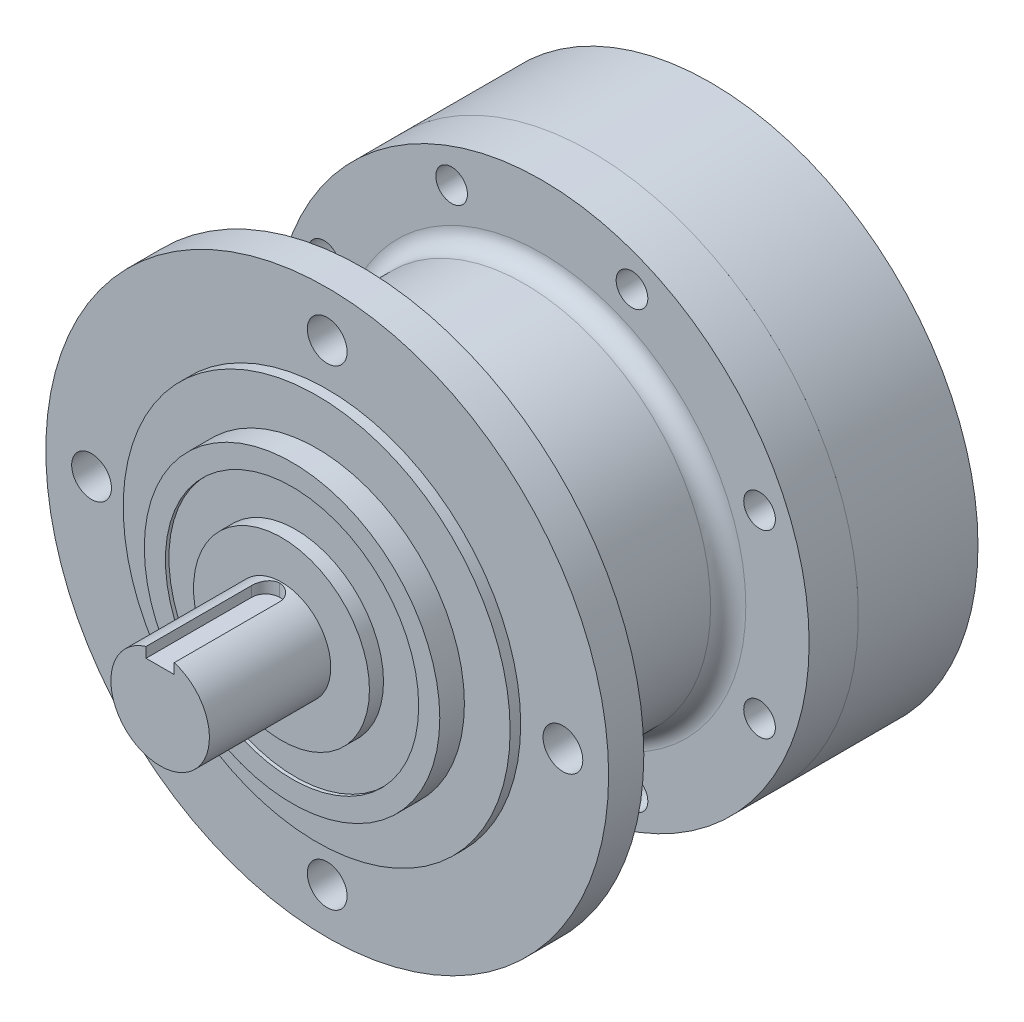
SolidWorks part; units mm, degrees
ref_plane "前视基准面" through (0, 0, 0) normal (0, 0, 1) x (1, 0, 0)
ref_plane "上视基准面" through (0, 0, 0) normal (0, 1, 0) x (1, 0, 0)
ref_plane "右视基准面" through (0, 0, 0) normal (1, 0, 0) x (0, 0, -1)
sketch "草图1" plane through (0, 0, 0) normal (0, 0, 1) x (1, 0, 0)
  circle A0 centre (0, 0) radius 76
  dimension "D1" = 152
extrude "拉伸1" add sketch "草图1" along normal blind 48
sketch "草图2" plane through (0, 0, 48) normal (0, 0, 1) x (1, 0, 0)
  circle A0 centre (0, 0) radius 53
extrude "拉伸2" add sketch "草图2" along normal blind 51
sketch "草图3" plane through (0, 0, 99) normal (0, 0, 1) x (1, 0, 0)
  circle A0 centre (0, 0) radius 80
extrude "拉伸3" add sketch "草图3" along normal blind 10
fillet "圆角1" radius 5 2 edges at (53, 0, 48) (53, 0, 99)
sketch "草图4" plane through (0, 0, 109) normal (0, 0, 1) x (1, 0, 0)
  circle A0 centre (0, 0) radius 55
extrude "拉伸4" add sketch "草图4" along normal blind 3
sketch "草图5" plane through (0, 0, 112) normal (0, 0, 1) x (1, 0, 0)
  circle A0 centre (0, 0) radius 42
extrude "拉伸5" add sketch "草图5" along normal blind 7
sketch "草图6" plane through (0, 0, 119) normal (0, 0, 1) x (1, 0, 0)
  circle A0 centre (0, 0) radius 25
extrude "拉伸6" add sketch "草图6" along normal blind 3
sketch "草图7" plane through (0, 0, 119) normal (0, 0, 1) x (1, 0, 0)
  circle A0 centre (0, 0) radius 36
  circle A1 centre (0, 0) radius 25
extrude "切除-拉伸1" cut sketch "草图7" against normal blind 1
sketch "草图8" plane through (0, 0, 122) normal (0, 0, 1) x (1, 0, 0)
  circle A0 centre (0, 0) radius 14
extrude "拉伸7" add sketch "草图8" along normal blind 34.5
sketch "草图9" plane through (0, 0, 156.5) normal (0, 0, 1) x (1, 0, 0)
  line L1 (-4, 14) -> (-4, 10.5)
  line L2 (4, 14) -> (4, 10.5)
  line L3 (-4, 14) -> (4, 14)
  line L9 (-4, 10.5) -> (4, 10.5)
extrude "切除-拉伸3" cut sketch "草图9" against normal blind 34
fillet "圆角2" radius 4 2 edges at (-4, 11.9582, 122.5) (4, 11.9582, 122.5)
sketch "草图10" plane through (0, 0, 109) normal (0, 0, 1) x (1, 0, 0)
  circle A1 centre (0, 67) radius 5.65
  circle A2 centre (67, 0) radius 5.65
  circle A3 centre (0, -67) radius 5.65
  circle A4 centre (-67, 0) radius 5.65
extrude "切除-拉伸4" cut sketch "草图10" against normal blind 14
sketch "草图11" plane through (0, 0, 0) normal (0, 0, -1) x (-1, 0, 0)
  circle A1 centre (61.8999, 25.6398) radius 4.5
  circle A2 centre (61.8999, -25.6398) radius 4.5
  circle A3 centre (25.6398, -61.8999) radius 4.5
  circle A4 centre (-25.6398, -61.8999) radius 4.5
  circle A5 centre (-61.8999, -25.6398) radius 4.5
  circle A6 centre (-61.8999, 25.6398) radius 4.5
  circle A7 centre (-25.6398, 61.8999) radius 4.5
  circle A8 centre (25.6398, 61.8999) radius 4.5
extrude "切除-拉伸5" cut sketch "草图11" against normal blind 74
ref_plane "基准面1" through (0, 0, 34) normal (0, 0, -1) x (-1, 0, 0)
sketch "草图12" plane through (0, 0, 34) normal (0, 0, -1) x (-1, 0, 0)
  circle A0 centre (0, 0) radius 76
extrude "切除-拉伸6" cut sketch "草图12" against normal blind 0.001
sketch "草图13" plane through (0, 0, 0) normal (0, 0, -1) x (-1, 0, 0)
  circle A0 centre (0, 0) radius 53.5
  circle A1 centre (0, 0) radius 52.5
  dimension "D1" = 105
extrude "切除-拉伸7" cut sketch "草图13" against normal blind 34
sketch "草图14" plane through (0, 0, 0) normal (0, 0, -1) x (-1, 0, 0)
  circle A0 centre (0, 0) radius 7.5
extrude "切除-拉伸8" cut sketch "草图14" against normal blind 27
sketch "草图15" plane through (0, 0, 0) normal (0, 0, -1) x (-1, 0, 0)
  line L5 (-2.5, 10) -> (2.5, 10)
  line L6 (-2.5, 7.0711) -> (-2.5, 10)
  line L11 (2.5, 7.0711) -> (2.5, 10)
  arc A4 (2.5, 7.0711) -> (-2.5, 7.0711) centre (0, 0) ccw
extrude "切除-拉伸9" cut sketch "草图15" against normal blind 27
